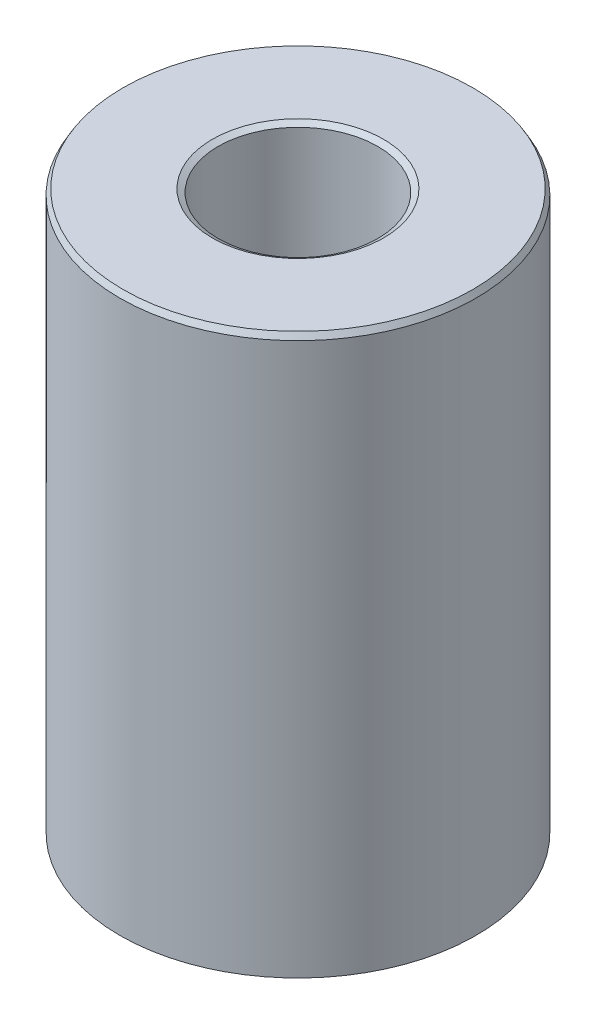
SolidWorks part; units mm, degrees
ref_plane "Front Plane" through (0, 0, 0) normal (0, 0, 1) x (1, 0, 0)
ref_plane "Top Plane" through (0, 0, 0) normal (0, 1, 0) x (1, 0, 0)
ref_plane "Right Plane" through (0, 0, 0) normal (1, 0, 0) x (0, 0, -1)
sketch "Sketch1" plane through (0, 0, 0) normal (0, 1, 0) x (1, 0, 0)
  circle A0 centre (0, 0) radius 55
  dimension "SLEEVE_OD" = 110
extrude "Boss-Extrude1" add sketch "Sketch1" along normal blind 173.2149
sketch "Sketch2" plane through (0, 0, 0) normal (0, 1, 0) x (1, 0, 0)
  circle A0 centre (0, 0) radius 24.6489
  dimension "BORE_D" = 49.2978
extrude "Cut-Extrude1" cut sketch "Sketch2" along normal through all
chamfer "Chamfer1" distance 1.7749 angle 30 4 edges at (0, 173.2149, 24.6489) (0, 0, 24.6489) (0, 0, 55) (0, 173.2149, 55) first distance on face at (0, 173.2149, 24.6489) first distance on face at (0, 0, 24.6489) first distance on face at (0, 173.2149, 55)
